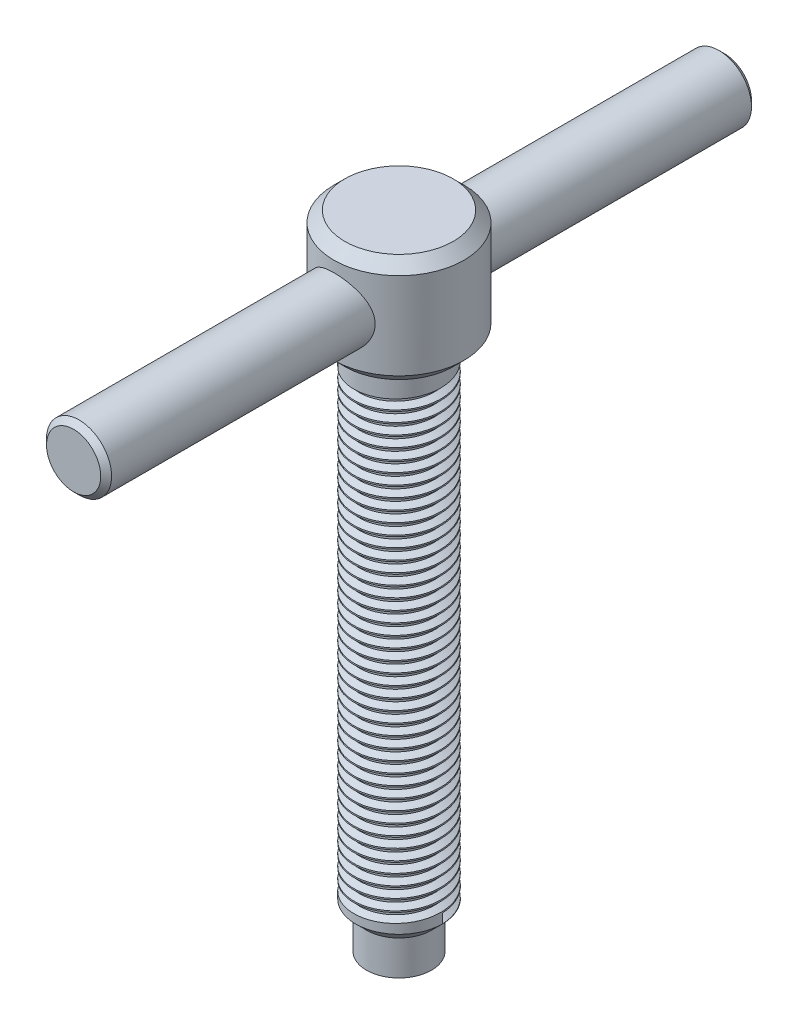
SolidWorks part; units mm, degrees
material "AISI 1045 钢，冷拔"
ref_plane "前视基准面" through (0, 0, 0) normal (0, 0, 1) x (1, 0, 0)
ref_plane "上视基准面" through (0, 0, 0) normal (0, 1, 0) x (1, 0, 0)
ref_plane "右视基准面" through (0, 0, 0) normal (1, 0, 0) x (0, 0, -1)
sketch "草图1" plane through (0, 0, 0) normal (0, 0, 1) x (1, 0, 0)
  line L2 (12, 0) -> (12, -20)
  line L5 (8, -20) -> (8, -112)
  line L7 (6, -112) -> (6, -118.3923)
  line L10 (0, 0) -> (0, -120)
  line L12 (6, -112) -> (8, -112)
  line L13 (8, -20) -> (12, -20)
  line L14 (0, 0) -> (12, 0)
  arc A0 (6, -118.3923) -> (0, -120) centre (0, -108) cw
  point P4 (10, -20)
  dimension "D10" = 12
  dimension "D2" = 100
  dimension "D3" = 8
  dimension "D4" = 20
  dimension "D5" = 6
  dimension "D6" = 12
  dimension "D11" = 8
revolve "旋转1" add sketch "草图1" angle 360 about L10
sketch "草图2" plane through (0, 0, 0) normal (0, 0, 1) x (1, 0, 0)
  line L8 (12, 0) -> (-12, 0) construction
  line L9 (-12, -20) -> (12, -20) construction
  line L10 (-12, 0) -> (-12, -20) construction
  line L11 (12, -20) -> (12, 0) construction
  line L12 (12, 0) -> (-12, 0)
  line L13 (-12, -20) -> (12, -20)
  line L14 (-12, 0) -> (-12, -20)
  line L15 (12, -20) -> (12, 0)
  circle A0 centre (0, -10) radius 6
  point P9 (12, -10)
  dimension "D1" = 12
extrude "凸台-拉伸1" add sketch "草图2" along normal mid plane 120 contours A0
chamfer "倒角1" distance 1 angle 45 2 edges at (6, -10, -60) (6, -10, 60)
chamfer "倒角3" distance 2 angle 45 3 edges at (-8, -112, 0) (-12, -20, 0) (-12, 0, 0)
thread "螺纹线1" pitch 2 method cut profile "螺纹线轮廓1" start angle 0, offset 0, length 85, pitch 2, diameter 16
ref_plane "基准面1" through (8, -110, 0) normal (0, 0, 1) x (1, 0, 0)
sketch "螺纹线轮廓1" plane through (8, -110, 0) normal (0, 0, 1) x (1, 0, 0)
  line L0 (0, 0) -> (0, 2) construction
  line L11 (0, 0) -> (0, 1.75)
  line L12 (0, 1.75) -> (-1.0825, 1.125)
  line L13 (-1.0825, 1.125) -> (-1.0825, 0.625)
  line L15 (-1.0825, 0.625) -> (0, 0)
  line L17 (-1.0825, 0.875) -> (0, 0.875) construction
  point P2 (0, 0)
  dimension "Pitch" = 2
  dimension "Profile_Angle" = 60
  dimension "Profile_Land" = 0.5
  dimension "Profile_Height" = 1.0825
